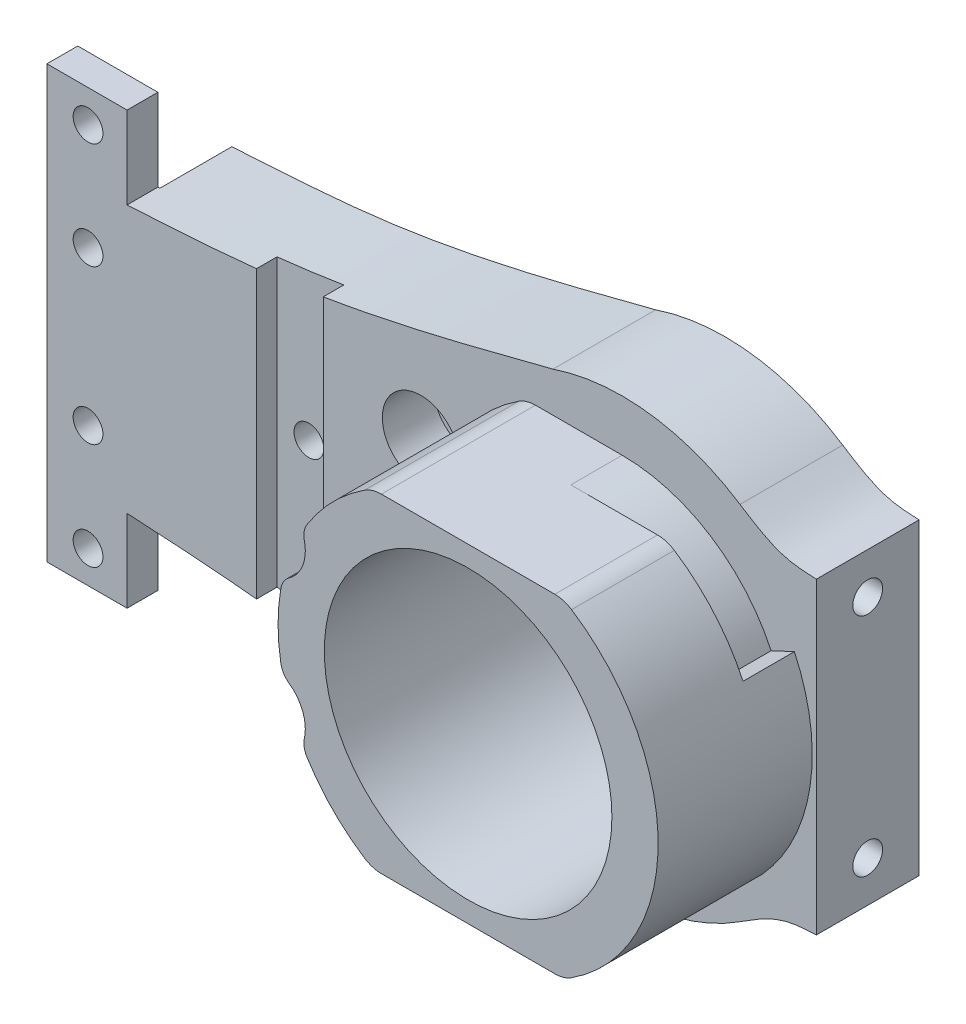
SolidWorks part; units mm, degrees
ref_plane "Front Plane" through (0, 0, 0) normal (0, 0, 1) x (1, 0, 0)
ref_plane "Top Plane" through (0, 0, 0) normal (0, 1, 0) x (1, 0, 0)
ref_plane "Right Plane" through (0, 0, 0) normal (1, 0, 0) x (0, 0, -1)
sketch "Sketch1" plane through (0, 0, 0) normal (0, 0, 1) x (1, 0, 0)
  line L0 (-30, 21) -> (-22.2, 21)
  line L1 (44.9, 15) -> (44.9, -15)
  line L2 (-22.2, 21) -> (-22.2, 13)
  line L3 (-30, -21) -> (-30, 21)
  line L4 (-30, 0) -> (0, 0) construction
  line L5 (0, 0) -> (44.9, 0) construction
  line L6 (-30, -21) -> (-22.2, -21)
  line L7 (-22.2, -21) -> (-22.2, -13)
  circle A0 centre (26, 0) radius 14
  arc A1 (19.2579, -19.8883) -> (37.4703, -17.5907) centre (26, 0) ccw
  arc A2 (37.4703, 17.5907) -> (19.2579, 19.8883) centre (26, 0) ccw
  spline S0 degree 3 poles (-22.2, 13) (-17.0873, 13.2934) (-3.0476, 14.0991) (10.5879, 17.6381) (19.2579, 19.8883) knots 0 0 0 0 0.364161 1 1 1 1
  spline S1 degree 3 poles (-22.2, -13) (-17.0873, -13.2934) (-3.0476, -14.0991) (10.5879, -17.6381) (19.2579, -19.8883) knots 0 0 0 0 0.364161 1 1 1 1
  spline S2 degree 3 poles (44.9, 15) (43.9598, 15.0415) (41.2679, 15.1604) (38.9674, 16.6326) (37.4703, 17.5907) knots 0 0 0 0 0.349252 1 1 1 1
  spline S3 degree 3 poles (44.9, -15) (43.9598, -15.0415) (41.2679, -15.1604) (38.9674, -16.6326) (37.4703, -17.5907) knots 0 0 0 0 0.349252 1 1 1 1
  dimension "D4" = 28
  dimension "D5" = 42
  dimension "D1" = 74.9
  dimension "D2" = 42
  dimension "D3" = 30
  dimension "D6" = 56
  dimension "D7" = 30
  dimension "D8" = 7.8
  dimension "D9" = 8
extrude "Extrude1" add sketch "Sketch1" along normal blind 10
sketch "Sketch3" plane through (0, 0, 10) normal (0, 0, 1) x (1, 0, 0)
  circle A0 centre (26, 0) radius 18.5
  circle A1 centre (26, 0) radius 14
  dimension "D1" = 37
extrude "Extrude2" add sketch "Sketch3" along normal blind 15
sketch "Sketch4" plane through (0, 0, 0) normal (0, 0, -1) x (-1, 0, 0)
  line L0 (30, 21) -> (30, -21) construction
  line L1 (30, 23.4126) -> (22, 23.4126)
  line L2 (30, 23.4126) -> (30, -25.9867)
  line L3 (30, -25.9867) -> (22, -25.9867)
  line L4 (22, 23.4126) -> (22, -25.9867)
  dimension "D1" = 8
extrude "Extrude3" cut sketch "Sketch4" against normal blind 7
hole_wizard "CBORE for M3 Pan Head Machine Screw1" positions "3DSketch1" profile "Sketch5" counterbore size "M3" standard "Ansi Metric" end condition through all
sketch3d "3DSketch1"
  line L0 (6.4, 7.5, 10) -> (6.4, -7.5, 10) construction
  line L3 (6.4, 0, 10) -> (0, 0, 10) construction
  line L4 (-30, 21, 10) -> (-30, -21, 10) construction
  point P0 (6.4, 7.5, 10)
  point P2 (6.4, -7.5, 10)
  dimension "D1" = 7.5
  dimension "D2" = 7.5
  dimension "D3" = 36.4
sketch "Sketch5" plane through (6.4, 7.5, 10) normal (1, 0, 0) x (0, -1, 0)
  line L0 (0, 0) -> (0, 10)
  line L1 (0, 10) -> (1.8, 10)
  line L3 (1.8, 10) -> (1.8, 5)
  line L4 (1.8, 5) -> (3.75, 5)
  line L5 (3.75, 5) -> (3.75, 0)
  line L7 (3.75, 0) -> (0, 0)
  line L11 (0, -6.35) -> (0, 107.95) construction
  dimension "Thru Hole Dia." = 3.6
  dimension "Thru Hole Depth" = 10
  dimension "C'Bore Dia." = 7.5
  dimension "C'Bore Depth" = 5
sketch "Sketch6" plane through (0, 0, 10) normal (0, 0, 1) x (1, 0, 0)
  circle A0 centre (6.4, 7.5) radius 3.75
  circle A1 centre (6.4, -7.5) radius 3.75
  circle A2 centre (6.4, 7.5) radius 3.75 construction
extrude "Extrude4" cut sketch "Sketch6" along normal blind 20
fillet "Fillet1" radius 2 4 edges at (9.8369, -9.0002, 17.5) (7.9575, 4.0887, 17.5) (9.8369, 9.0002, 17.5) (7.9575, -4.0887, 17.5)
sketch "Sketch8" plane through (0, 0, 25) normal (0, 0, 1) x (1, 0, 0)
  line L0 (0, 0) -> (9, 0) construction
  line L1 (16.7129, 16) -> (35.2871, 16)
  line L2 (16.7129, 16) -> (16.7129, 23.4488)
  line L3 (16.7129, 23.4488) -> (35.2871, 23.4488)
  line L4 (35.2871, 16) -> (35.2871, 23.4488)
  line L5 (26, 0) -> (26, 26.3314) construction
  line L6 (16.7129, -23.4488) -> (35.2871, -23.4488)
  line L7 (35.2871, -16) -> (35.2871, -23.4488)
  line L8 (16.7129, -16) -> (35.2871, -16)
  line L9 (16.7129, -16) -> (16.7129, -23.4488)
  circle A0 centre (26, 0) radius 18.5 construction
  point P13 (26, 16)
  dimension "D1" = 16
extrude "Extrude5" cut sketch "Sketch8" against normal up to surface (15 mm away) up to face at (4.5821, 0.3581, 10)
fillet "Fillet2" radius 3 4 edges at (16.7129, -16, 17.5) (35.2871, -16, 17.5) (35.2871, 16, 17.5) (16.7129, 16, 17.5)
sketch "Sketch11" plane through (0, 0, 10) normal (0, 0, 1) x (1, 0, 0)
  line L0 (17.559, 16) -> (34.441, 16) construction
  line L1 (26, 16) -> (26, 19)
  line L2 (40.4989, 6.7663) -> (43.2174, 8.0349)
  line L3 (26, -16) -> (26, -19)
  line L5 (40.4989, 6.7663) -> (8.7826, -8.0349) construction
  line L6 (8.7826, -8.0349) -> (11.5011, -6.7663)
  arc A0 (11.5011, -6.7663) -> (26, -16) centre (26, 0) ccw
  arc A1 (8.7826, -8.0349) -> (26, -19) centre (26, 0) ccw
  arc A2 (40.4989, 6.7663) -> (26, 16) centre (26, 0) ccw
  arc A3 (43.2174, 8.0349) -> (26, 19) centre (26, 0) ccw
  dimension "D1" = 35
extrude "Extrude8" cut sketch "Sketch11" along normal blind 5
hole_wizard "Ø2.9 (2.9) Diameter Hole1" positions "3DSketch2" profile "Sketch13" hole size "Ø2.9" standard "Ansi Metric"
sketch3d "3DSketch2"
  line L0 (-26, -21, 10) -> (-26, 21, 10) construction
  line L1 (-30, -21, 10) -> (-22.2, -21, 10) construction
  line L2 (-22.2, 21, 10) -> (-30, 21, 10) construction
  line L6 (-30, 21, 10) -> (-30, -21, 10) construction
  point P0 (-26, -17.85, 10)
  point P2 (-26, -7.5, 10)
  point P4 (-26, 7.5, 10)
  point P6 (-26, 17.85, 10)
  point P22 (-26, 0, 10)
  dimension "D1" = 15
  dimension "D2" = 7.5
  dimension "D3" = 3.15
  dimension "D4" = 3.15
  dimension "D5" = 4
sketch "Sketch13" plane through (-26, -17.85, 10) normal (1, 0, 0) x (0, -1, 0)
  line L0 (0, 0) -> (0, 10)
  line L1 (0, 10) -> (1.45, 10)
  line L2 (1.45, 10) -> (1.45, 0)
  line L5 (1.45, 0) -> (0, 0)
  line L10 (0, 10) -> (-1.45, 10) construction
  line L11 (0, -6.35) -> (0, 107.95) construction
  dimension "Hole Dia." = 2.9
  dimension "Hole Depth" = 10
  dimension "Drill Angle" = 180
sketch "Sketch14" plane through (0, 0, 10) normal (0, 0, 1) x (1, 0, 0)
  line L0 (-30, 21) -> (-30, -21) construction
  line L1 (-3.1, -23.334) -> (-9.6, -23.334)
  line L2 (-3.1, -23.334) -> (-3.1, 21.2199)
  line L3 (-3.1, 21.2199) -> (-9.6, 21.2199)
  line L4 (-9.6, -23.334) -> (-9.6, 21.2199)
  dimension "D1" = 6.5
  dimension "D2" = 20.4
extrude "Extrude9" cut sketch "Sketch14" against normal blind 2
sketch "Sketch15" plane through (0, 0, 8) normal (0, 0, 1) x (1, 0, 0)
  line L0 (-6.5, -14.2974) -> (-6.5, 14.2974) construction
  line L1 (-9.6, 13.9272) -> (-9.6, -13.9272) construction
  circle A0 centre (-6.5, 0) radius 1.45
  spline S0 degree 3 poles (-9.6, -13.9272) (-8.7037, -14.0224) (-6.5313, -14.276) (-4.3688, -14.5963) (-3.1, -14.8043) knots 0.299863 0.299863 0.299863 0.299863 0.364161 0.455943 0.455943 0.455943 0.455943 construction
  spline S1 degree 3 poles (-3.1, 14.8043) (-4.3688, 14.5963) (-6.5313, 14.276) (-8.7037, 14.0224) (-9.6, 13.9272) knots 0.544057 0.544057 0.544057 0.544057 0.635839 0.700137 0.700137 0.700137 0.700137 construction
  point P8 (-6.5, 0)
  dimension "D1" = 2.9
  dimension "D2" = 3.1
extrude "Extrude10" cut sketch "Sketch15" against normal blind 10
sketch "Sketch16" plane through (44.9, 0, 0) normal (1, 0, 0) x (0, 0, -1)
  line L0 (-5, -15) -> (-5, 15) construction
  line L2 (-10, 15) -> (0, 15) construction
  line L3 (-10, -15) -> (-10, 15) construction
  circle A0 centre (-5, -11) radius 1.45
  circle A1 centre (-5, 11) radius 1.45
  dimension "D1" = 2.9
  dimension "D2" = 4
  dimension "D3" = 4
  dimension "D4" = 5
extrude "Extrude11" cut sketch "Sketch16" against normal blind 6
